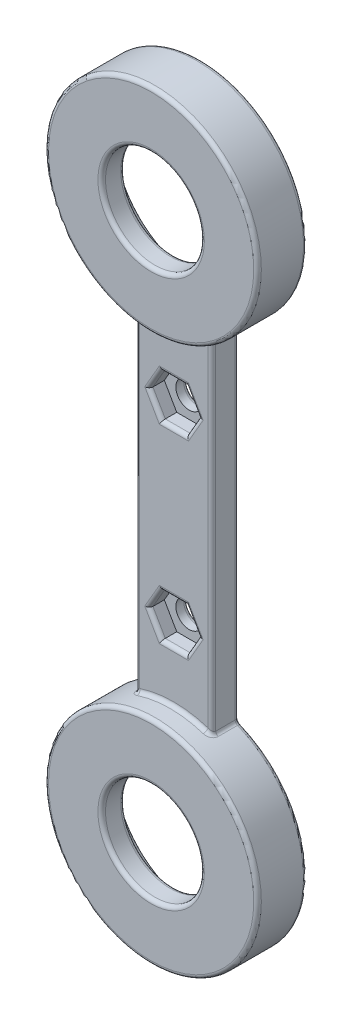
SolidWorks part; units mm, degrees
ref_plane "Front Plane" through (0, 0, 0) normal (0, 0, 1) x (1, 0, 0)
ref_plane "Top Plane" through (0, 0, 0) normal (0, 1, 0) x (1, 0, 0)
ref_plane "Right Plane" through (0, 0, 0) normal (1, 0, 0) x (0, 0, -1)
sketch "Sketch1" plane through (0, 0, 0) normal (0, 0, 1) x (1, 0, 0)
  line L0 (0, 11) -> (0, 36)
  line L1 (0, 36) -> (5, 36)
  line L2 (5, 36) -> (5, 13.0767)
  line L3 (0, 0) -> (14, 0) construction
  line L4 (0, 36) -> (-5, 36)
  line L5 (-5, 36) -> (-5, 13.0767)
  line L7 (-3.262, 23.5) -> (-1.631, 20.675)
  line L8 (-1.631, 20.675) -> (1.631, 20.675)
  line L9 (1.631, 20.675) -> (3.262, 23.5)
  line L10 (3.262, 23.5) -> (1.631, 26.325)
  line L11 (1.631, 26.325) -> (-1.631, 26.325)
  line L12 (-1.631, 26.325) -> (-3.262, 23.5)
  circle A0 centre (0, 0) radius 11 construction
  circle A1 centre (0, 0) radius 14
  circle A2 centre (0, 0) radius 11.15
  circle A3 centre (0, 0) radius 6.5
  circle A5 centre (0, 23.5) radius 2.825 construction
  circle A6 centre (0, 23.5) radius 1.75
  dimension "D1" = 22
  dimension "D2" = 28
  dimension "D6" = 13
  dimension "D8" = 5.65
  dimension "D9" = 3.5
  dimension "D3" = 25
  dimension "D4" = 5
  dimension "D7" = 5
  dimension "D5" = 0.15
extrude "Boss-Extrude1" add sketch "Sketch1" along normal blind 3 contours A1 A2 | A2 A3 region at (2.4704, 13.3778, 0) region at (7.6612, 7.6612, 0)
extrude "Boss-Extrude2" add sketch "Sketch1<4>" against normal blind 3.55 contours A1 A2 | A1 L0 L4 L5 | A1 L2 L1 L0 | L7 L8 L9 L10 L11 L12 region at (2.4704, 13.3778, 0) region at (-2.6938, 25.037, 0) region at (2.6938, 25.037, 0)
sketch "Sketch1<4>" plane through (0, 0, 0) normal (0, 0, 1) x (1, 0, 0) same geometry as "Sketch1"
extrude "Cut-Extrude2" cut sketch "Sketch1<7>" against normal through all contours L0 A6 | L0 A6 region at (-0.7427, 23.5, 0) region at (0.7427, 23.5, 0)
sketch "Sketch1<7>" plane through (0, 0, 0) normal (0, 0, 1) x (1, 0, 0) same geometry as "Sketch1"
extrude "Cut-Extrude3" cut sketch "Sketch1<8>" against normal blind 2 contours A6 L0 L8 L9 L10 L11 | A6 L0 L11 L12 L7 L8 region at (-0.8155, 20.7402, 0) region at (0.0652, 21.2125, 0)
sketch "Sketch1<8>" plane through (0, 0, 0) normal (0, 0, 1) x (1, 0, 0) same geometry as "Sketch1"
mirror "Mirror4" about plane through (0, 36, -3.55) normal (0, -1, 0) of bodies 111
fillet "Fillet1" radius 0.5 34 edges at (-5, 58.9233, -1.775) (-5, 13.0767, -1.775) (5, 58.9233, -1.775) (5, 13.0767, -1.775) (-2.4465, 47.0875, 0) (0, 45.675, 0) (2.4465, 47.0875, 0) (2.4465, 49.9125, 0) (0, 51.325, 0) (-2.4465, 49.9125, 0) (-5, 36, 0) (0, 58, 0) (5, 36, 0) (0, 14, 0) (0, 20.675, 0) (2.4465, 22.0875, 0) (2.4465, 24.9125, 0) (0, 26.325, 0) (-2.4465, 24.9125, 0) (-2.4465, 22.0875, 0) (6.5, 0, 3) (14, 0, 3) (6.5, 72, 3) (14, 72, 3) (11.15, 72, -3.55) (1.75, 48.5, -3.55) (11.15, 0, -3.55) (0, -14, -3.55) (5, 36, -3.55) (0, 86, -3.55) (-5, 36, -3.55) (1.75, 23.5, -3.55) (6.5, 72, 0) (6.5, 0, 0)
